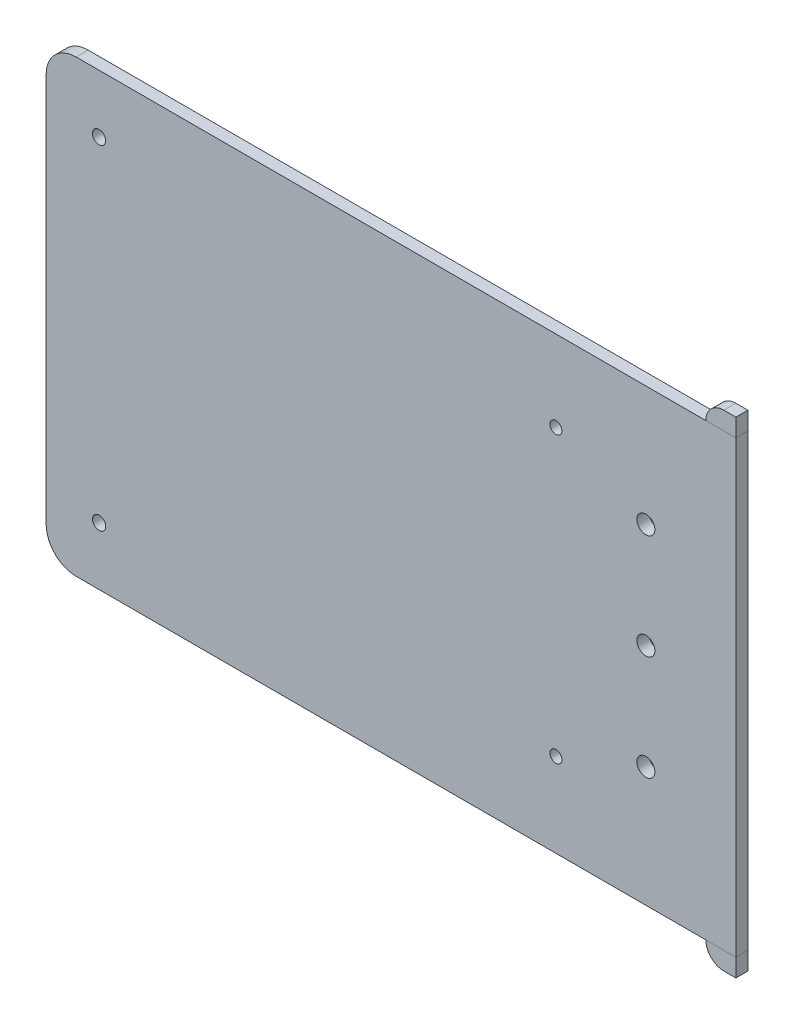
SolidWorks part; units mm, degrees
ref_plane "Plan de face" through (0, 0, 0) normal (0, 0, 1) x (1, 0, 0)
ref_plane "Plan de dessus" through (0, 0, 0) normal (0, 1, 0) x (1, 0, 0)
ref_plane "Plan de droite" through (0, 0, 0) normal (1, 0, 0) x (0, 0, -1)
sketch "Sketch1" plane through (0, 0, 0) normal (0, 0, 1) x (1, 0, 0)
  line L1 (0, 0) -> (230, 0)
  line L2 (0, 0) -> (0, 75)
  line L3 (0, 75) -> (230, 75)
  line L4 (230, 0) -> (230, 75)
  dimension "D1" = 230
  dimension "D2" = 75
extrude "Boss-Extrude1" add sketch "Sketch1" along normal blind 2
sketch "Sketch2" plane through (0, 0, 0) normal (0, 0, -1) x (-1, 0, 0)
  line L0 (-9.0685, 28.6546) -> (-9.0685, 48.2614) construction
  text T0 "BOTTOM"
extrude "Cut-Extrude1" cut sketch "Sketch2" against normal blind 1
fillet "Fillet1" radius 5 4 edges at (0, 0, 1) (230, 0, 1) (0, 75, 1) (230, 75, 1)
sketch "Sketch4" plane through (0, 0, 0) normal (0, 0, -1) x (-1, 0, 0)
  line L0 (-230, 5) -> (-230, 70) construction
  line L1 (-225, 75) -> (-110, 75)
  line L2 (-225, 75) -> (-225, 78)
  line L3 (-225, 78) -> (-110, 78)
  line L4 (-110, 75) -> (-110, 78)
  line L5 (-225, 0) -> (-110, 0)
  line L6 (-225, 0) -> (-225, -3)
  line L7 (-225, -3) -> (-110, -3)
  line L8 (-110, 0) -> (-110, -3)
  dimension "D1" = 3
  dimension "D2" = 3
  dimension "D3" = 120
  dimension "D4" = 120
extrude "Boss-Extrude2" add sketch "Sketch4" against normal blind 2 separate body
fillet "Fillet4" radius 3 1 edges at (225, 78, 1)
fillet "Fillet5" radius 3 2 edges at (110, -3, 1) (225, -3, 1)
fillet "Fillet6" radius 3 1 edges at (110, 78, 1)
sketch "Sketch5" plane through (0, 0, 0) normal (0, 0, -1) x (-1, 0, 0)
  line L0 (0, 70) -> (0, 5) construction
  line L1 (-5, 0) -> (-225, 0) construction
  line L2 (-225, 75) -> (-5, 75) construction
  line L3 (-230, 5) -> (-230, 70) construction
  line L4 (-222, -3) -> (-113, -3) construction
  line L5 (-113, 78) -> (-222, 78) construction
  circle A0 centre (-8.82, 9.65) radius 1.1
  circle A1 centre (-8.82, 65.35) radius 1.1
  circle A2 centre (-118.46, 71.81) radius 1.1
  circle A3 centre (-118.46, 3.19) radius 1.1
  circle A4 centre (-211.07, 1.6) radius 1.1
  circle A5 centre (-211.17, 73.4) radius 1.1
  dimension "D1" = 2.2
  dimension "D2" = 2.2
  dimension "D3" = 8.82
  dimension "D4" = 9.65
  dimension "D5" = 9.65
  dimension "D7" = 2.2
  dimension "D8" = 2.2
  dimension "D9" = 2.2
  dimension "D10" = 2.2
  dimension "D16" = 6.19
  dimension "D17" = 6.19
  dimension "D18" = 4.6
  dimension "D6" = 8.82
  dimension "D11" = 111.54
  dimension "D12" = 111.54
  dimension "D13" = 18.83
  dimension "D14" = 18.93
  dimension "D15" = 4.6
extrude "Cut-Extrude2" cut sketch "Sketch5" against normal through all
sketch "Sketch6" plane through (0, 0, 0) normal (0, 0, -1) x (-1, 0, 0)
  line L0 (-113, 78) -> (-222, 78) construction
  line L1 (-230, 5) -> (-230, 70) construction
  line L2 (-222, -3) -> (-113, -3) construction
  circle A0 centre (-70.1716, 14.8056) radius 4.237
  circle A1 centre (-70.1716, 28.7182) radius 4.6376
  circle A2 centre (-70.1716, 52.7492) radius 4.1522
  circle A3 centre (-70.1716, 62.8675) radius 6.3239
  circle A4 centre (-186.05, 73) radius 1.5
  circle A5 centre (-186.05, 63) radius 1.5
  circle A6 centre (-186.05, 12) radius 1.5
  circle A7 centre (-186.05, 2) radius 1.5
  dimension "D1" = 3
  dimension "D2" = 3
  dimension "D3" = 3
  dimension "D4" = 3
  dimension "D5" = 5
  dimension "D6" = 10
  dimension "D7" = 43.95
  dimension "D8" = 43.95
  dimension "D9" = 10
  dimension "D10" = 5
extrude "Cut-Extrude3" cut sketch "Sketch6" against normal through all contours A6 | A5 | A7 | A4 region at (186.05, 73, 0) region at (186.05, 63, 0) region at (186.05, 12, 0) region at (186.05, 2, 0)
sketch "Sketch7" plane through (0, 0, 0) normal (0, 0, -1) x (-1, 0, 0)
  line L0 (-225, 75) -> (-5, 75) construction
  line L1 (-5, 0) -> (-225, 0) construction
  line L2 (-230, 5) -> (-230, 70) construction
  line L4 (0, 70) -> (0, 5) construction
  circle A0 centre (-130, 20) radius 1.5
  circle A1 centre (-130, 55) radius 1.5
  circle A2 centre (-100, 20) radius 1.5
  circle A3 centre (-100, 55) radius 1.5
  circle A4 centre (-100, 37.5) radius 1.5
  circle A5 centre (-130, 37.5) radius 1.5
  dimension "D1" = 3
  dimension "D2" = 3
  dimension "D3" = 3
  dimension "D4" = 3
  dimension "D5" = 3
  dimension "D6" = 3
  dimension "D7" = 20
  dimension "D8" = 20
  dimension "D9" = 20
  dimension "D10" = 20
  dimension "D11" = 100
  dimension "D12" = 100
  dimension "D13" = 17.5
extrude "Cut-Extrude4" cut sketch "Sketch7" against normal through all
sketch "Sketch8" plane through (0, 0, 0) normal (0, 0, -1) x (-1, 0, 0)
  line L0 (0, 70) -> (0, 5) construction
  line L1 (-225, 75) -> (-5, 75) construction
  circle A0 centre (-85, 61.5) radius 1
  circle A1 centre (-85, 14) radius 1
  circle A2 centre (-141.75, 14) radius 1
  circle A3 centre (-141.75, 61.5) radius 1
  dimension "D1" = 2
  dimension "D2" = 2
  dimension "D3" = 2
  dimension "D4" = 2
  dimension "D5" = 85
  dimension "D7" = 13.5
  dimension "D6" = 56.75
  dimension "D8" = 47.5
extrude "Cut-Extrude5" cut sketch "Sketch8" against normal through all
sketch "Sketch10" plane through (0, 0, 0) normal (0, 0, -1) x (-1, 0, 0)
  line L0 (-230, 5) -> (-230, 70) construction
  line L1 (-230, 103.4528) -> (-115, 103.4528)
  line L2 (-230, 103.4528) -> (-230, -18.654)
  line L3 (-230, -18.654) -> (-115, -18.654)
  line L4 (-115, 103.4528) -> (-115, -18.654)
  dimension "D1" = 115
extrude "Cut-Extrude7" cut sketch "Sketch10" against normal blind 10
